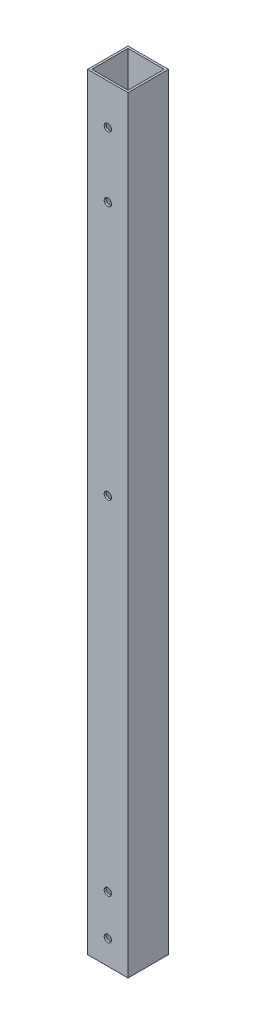
SolidWorks part; units mm, degrees
ref_plane "Front Plane" through (0, 0, 0) normal (0, 0, 1) x (1, 0, 0)
ref_plane "Top Plane" through (0, 0, 0) normal (0, 1, 0) x (1, 0, 0)
ref_plane "Right Plane" through (0, 0, 0) normal (1, 0, 0) x (0, 0, -1)
sketch "Sketch1" plane through (0, 0, 0) normal (0, 1, 0) x (1, 0, 0)
  line L0 (0, 0) -> (0, 25.4)
  line L1 (0, 25.4) -> (25.4, 25.4)
  line L2 (25.4, 25.4) -> (25.4, 0)
  line L3 (25.4, 0) -> (0, 0)
  line L6 (1.27, 12.3615) -> (1.27, 24.13)
  line L7 (1.27, 24.13) -> (12.7, 24.13)
  line L10 (12.7, 24.13) -> (24.13, 24.13)
  line L11 (24.13, 24.13) -> (24.13, 12.7)
  line L12 (24.13, 1.27) -> (24.13, 12.7)
  line L13 (24.13, 1.27) -> (12.7, 1.27)
  line L14 (1.27, 1.27) -> (12.7, 1.27)
  line L15 (1.27, 12.3615) -> (1.27, 1.27)
  dimension "D1" = 25.4
  dimension "D2" = 25.4
  dimension "D3" = 11.7685
  dimension "D4" = 11.0915
  dimension "D5" = 11.43
  dimension "D6" = 11.43
extrude "Boss-Extrude1" add sketch "Sketch1" along normal blind 482.6
sketch "Sketch2" plane through (0, 0, -25.4) normal (0, 0, -1) x (-1, 0, 0)
  line L0 (-25.4, 482.6) -> (0, 482.6) construction
  line L1 (-25.4, 482.6) -> (-25.4, 0) construction
  circle A0 centre (-12.7, 416.56) radius 2.286
  dimension "D3" = 4.572
  dimension "D1" = 66.04
  dimension "D2" = 12.7
extrude "Cut-Extrude1" cut sketch "Sketch2" against normal through all
sketch "Sketch3" plane through (0, 0, -25.4) normal (0, 0, -1) x (-1, 0, 0)
  line L1 (-25.4, 482.6) -> (-25.4, 0) construction
  line L2 (-25.4, 482.6) -> (0, 482.6) construction
  circle A0 centre (-12.7, 40.64) radius 2.286
  dimension "D3" = 4.572
  dimension "D1" = 441.96
  dimension "D2" = 12.7
extrude "Cut-Extrude2" cut sketch "Sketch3" against normal through all
sketch "Sketch4" plane through (0, 0, -25.4) normal (0, 0, -1) x (-1, 0, 0)
  line L0 (-25.4, 482.6) -> (0, 482.6) construction
  line L1 (-25.4, 482.6) -> (-25.4, 0) construction
  circle A0 centre (-12.7, 256.54) radius 2.286
  dimension "D2" = 4.572
  dimension "D1" = 226.06
  dimension "D3" = 12.7
extrude "Cut-Extrude3" cut sketch "Sketch4" against normal through all
sketch "Sketch6" plane through (0, 0, -25.4) normal (0, 0, -1) x (-1, 0, 0)
  line L0 (-25.4, 482.6) -> (-25.4, 0) construction
  line L1 (-25.4, 482.6) -> (0, 482.6) construction
  circle A0 centre (-12.7, 457.2) radius 2.286
  dimension "D3" = 4.572
  dimension "D1" = 12.7
  dimension "D2" = 25.4
extrude "Cut-Extrude5" cut sketch "Sketch6" against normal through all
sketch "Sketch7" plane through (0, 0, -25.4) normal (0, 0, -1) x (-1, 0, 0)
  line L0 (-25.4, 482.6) -> (-25.4, 0) construction
  line L1 (-25.4, 0) -> (0, 0) construction
  circle A0 centre (-12.7, 15.24) radius 2.286
  dimension "D3" = 4.572
  dimension "D1" = 12.7
  dimension "D2" = 15.24
extrude "Cut-Extrude6" cut sketch "Sketch7" against normal through all
